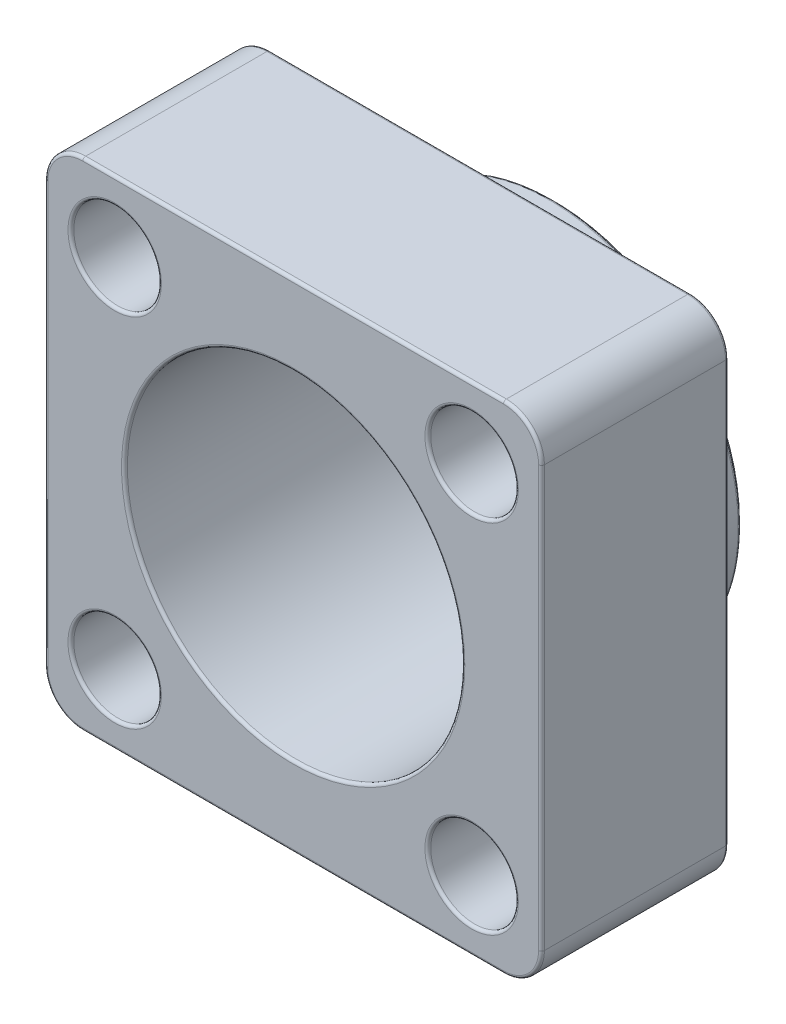
SolidWorks part; units mm, degrees
material "moto_black"
ref_plane "Front Plane" through (0, 0, 0) normal (0, 0, 1) x (1, 0, 0)
ref_plane "Top Plane" through (0, 0, 0) normal (0, 1, 0) x (1, 0, 0)
ref_plane "Right Plane" through (0, 0, 0) normal (1, 0, 0) x (0, 0, -1)
sketch "Sketch1" plane through (0, 0, 0) normal (0, 0, 1) x (1, 0, 0)
  line L0 (0, 0) -> (0, -27.5504)
  line L1 (-72, -85) -> (72, -85)
  line L2 (-85, -72) -> (-85, 72)
  line L3 (-72, 85) -> (72, 85)
  line L4 (85, -72) -> (85, 72)
  line L5 (-85, -85) -> (85, 85) construction
  line L6 (-85, 85) -> (85, -85) construction
  line L7 (0, -27.5504) -> (0, 0)
  line L8 (0, 0) -> (23.1269, 0)
  arc A0 (-72, -85) -> (-85, -72) centre (-72, -72) cw
  arc A1 (72, -85) -> (85, -72) centre (72, -72) ccw
  arc A2 (72, 85) -> (85, 72) centre (72, 72) cw
  arc A3 (-85, 72) -> (-72, 85) centre (-72, 72) cw
  circle A4 centre (0, 0) radius 57.75
  circle A5 centre (-61.0879, 61.0879) radius 15
  circle A6 centre (61.0879, 61.0879) radius 15
  circle A7 centre (61.0879, -61.0879) radius 15
  circle A8 centre (-61.0879, -61.0879) radius 15
  point P0 (0, 0)
  dimension "D3" = 13
  dimension "D4" = 115.5
  dimension "D5" = 30
  dimension "D1" = 170
  dimension "D2" = 170
extrude "Boss-Extrude1" add sketch "Sketch1" along normal mid plane 60 contours A3 L2 A0 L1 A1 L4 A2 L3 A6 A5 A4 A7 A8 region at (-79.4924, -79.4924, 0)
sketch "Sketch2" plane through (0, 0, -30) normal (0, 0, -1) x (-1, 0, 0)
  line L0 (-85, 72) -> (-85, -72)
  line L1 (-72, -85) -> (72, -85)
  line L2 (85, -72) -> (85, 72)
  line L3 (72, 85) -> (-72, 85)
  line L8 (79, -72) -> (79, 72)
  line L9 (-72, -79) -> (72, -79)
  line L10 (-79, 72) -> (-79, -72)
  line L11 (72, 79) -> (-72, 79)
  line L12 (79, -72) -> (79, 72)
  line L13 (-72, -79) -> (72, -79)
  line L14 (-79, 72) -> (-79, -72)
  line L15 (72, 79) -> (-72, 79)
  arc A0 (-72, 85) -> (-85, 72) centre (-72, 72) ccw
  arc A1 (-85, -72) -> (-72, -85) centre (-72, -72) ccw
  circle A2 centre (0, 0) radius 64.75
  circle A3 centre (0, 0) radius 64.75
  arc A4 (72, -85) -> (85, -72) centre (72, -72) ccw
  arc A5 (85, 72) -> (72, 85) centre (72, 72) ccw
  circle A6 centre (0, 0) radius 57.75
  arc A10 (79, 72) -> (72, 79) centre (72, 72) ccw
  arc A11 (72, -79) -> (79, -72) centre (72, -72) ccw
  arc A12 (-79, -72) -> (-72, -79) centre (-72, -72) ccw
  arc A13 (-72, 79) -> (-79, 72) centre (-72, 72) ccw
  arc A14 (79, 72) -> (72, 79) centre (72, 72) ccw
  arc A15 (72, -79) -> (79, -72) centre (72, -72) ccw
  arc A16 (-79, -72) -> (-72, -79) centre (-72, -72) ccw
  arc A17 (-72, 79) -> (-79, 72) centre (-72, 72) ccw
  circle M21 centre (0, 0) radius 57.75
  arc M22 (85, 72) -> (72, 85) centre (72, 72) ccw
  line M23 (72, 85) -> (-72, 85)
  arc M24 (-72, 85) -> (-85, 72) centre (-72, 72) ccw
  line M25 (-85, 72) -> (-85, -72)
  arc M26 (-85, -72) -> (-72, -85) centre (-72, -72) ccw
  line M27 (-72, -85) -> (72, -85)
  arc M28 (72, -85) -> (85, -72) centre (72, -72) ccw
  line M29 (85, -72) -> (85, 72)
  dimension "D1" = 7
  dimension "D2" = 6
  dimension "D3" = 6
  dimension "D4" = 7
extrude "Boss-Extrude4" add sketch "Sketch2" along normal blind 4 contours A17 L15 A14 L12 A15 L13 A16 L14 M29 M22 M23 M24 M25 M26 M27 M28 region at (79.4924, 79.4924, -30)
extrude "Boss-Extrude5" add sketch "Sketch2<5>" along normal blind 15 contours A3 M21 region at (62.9186, 0, -30)
sketch "Sketch2<5>" plane through (0, 0, -30) normal (0, 0, -1) x (-1, 0, 0) same geometry as "Sketch2"
sketch "Sketch3" plane through (0, 0, -45) normal (0, 0, -1) x (-1, 0, 0)
  circle A1 centre (0, 0) radius 69.049
  circle A2 centre (0, 0) radius 57.75
extrude "Boss-Extrude6" add sketch "Sketch3" along normal blind 4
sketch "Sketch4" plane through (0, 0, -49) normal (0, 0, -1) x (-1, 0, 0)
  circle A0 centre (0, 0) radius 64.75
  circle A1 centre (0, 0) radius 57.75
extrude "Boss-Extrude7" add sketch "Sketch4" along normal blind 11
fillet "Fillet2" radius 1 1 edges at (64.75, 0, -30)
fillet "Fillet3" radius 1 10 edges at (-76.9497, 76.9497, -30) (-79, 0, -30) (-76.9497, -76.9497, -30) (0, -79, -30) (76.9497, -76.9497, -30) (79, 0, -30) (76.9497, 76.9497, -30) (0, 79, -30) (-64.75, 0, -45) (-64.75, 0, -49)
fillet "Fillet4" radius 1 2 edges at (-69.049, 0, -45) (-69.049, 0, -49)
chamfer "Chamfer1" distance 2 angle 45 2 edges at (-57.75, 0, -60) (-64.75, 0, -60)
fillet "Fillet5" radius 1 4 edges at (-57.75, 0, -58) (-64.75, 0, -58) (-59.75, 0, -60) (-62.75, 0, -60)
fillet "Fillet6" radius 1 16 edges at (-81.1924, -81.1924, -34) (0, -85, -34) (81.1924, -81.1924, -34) (85, 0, -34) (81.1924, 81.1924, -34) (0, 85, -34) (-81.1924, 81.1924, -34) (-85, 0, -34) (79, 0, -34) (76.9497, -76.9497, -34) (0, -79, -34) (-76.9497, -76.9497, -34) (-79, 0, -34) (-76.9497, 76.9497, -34) (0, 79, -34) (76.9497, 76.9497, -34)
fillet "Fillet7" radius 1 4 edges at (-46.0879, -61.0879, -30) (76.0879, -61.0879, -30) (76.0879, 61.0879, -30) (-46.0879, 61.0879, -30)
fillet "Fillet8" radius 1 13 edges at (-46.0879, -61.0879, 30) (76.0879, -61.0879, 30) (0, 85, 30) (81.1924, 81.1924, 30) (85, 0, 30) (81.1924, -81.1924, 30) (0, -85, 30) (-81.1924, -81.1924, 30) (-85, 0, 30) (-81.1924, 81.1924, 30) (57.75, 0, 30) (-46.0879, 61.0879, 30) (76.0879, 61.0879, 30)
sketch "Sketch5" plane through (-85, 0, 0) normal (-1, 0, 0) x (0, 0, 1)
  line L1 (-24.5696, 57.5116) -> (6.1392, 57.5116)
  line L2 (-26.5696, 55.5116) -> (-26.5696, -55.5116)
  line L3 (-24.5696, -57.5116) -> (6.1392, -57.5116)
  line L4 (8.1392, 55.5116) -> (8.1392, -55.5116)
  line L5 (-26.5696, 57.5116) -> (8.1392, -57.5116) construction
  line L6 (-26.5696, -57.5116) -> (8.1392, 57.5116) construction
  arc A0 (6.1392, -57.5116) -> (8.1392, -55.5116) centre (6.1392, -55.5116) ccw
  arc A1 (-26.5696, -55.5116) -> (-24.5696, -57.5116) centre (-24.5696, -55.5116) ccw
  arc A2 (6.1392, 57.5116) -> (8.1392, 55.5116) centre (6.1392, 55.5116) cw
  arc A3 (-24.5696, 57.5116) -> (-26.5696, 55.5116) centre (-24.5696, 55.5116) ccw
  point P0 (-9.2152, 0)
  dimension "D1" = 2
extrude "Cut-Extrude1" cut sketch "Sketch5" against normal blind 2
